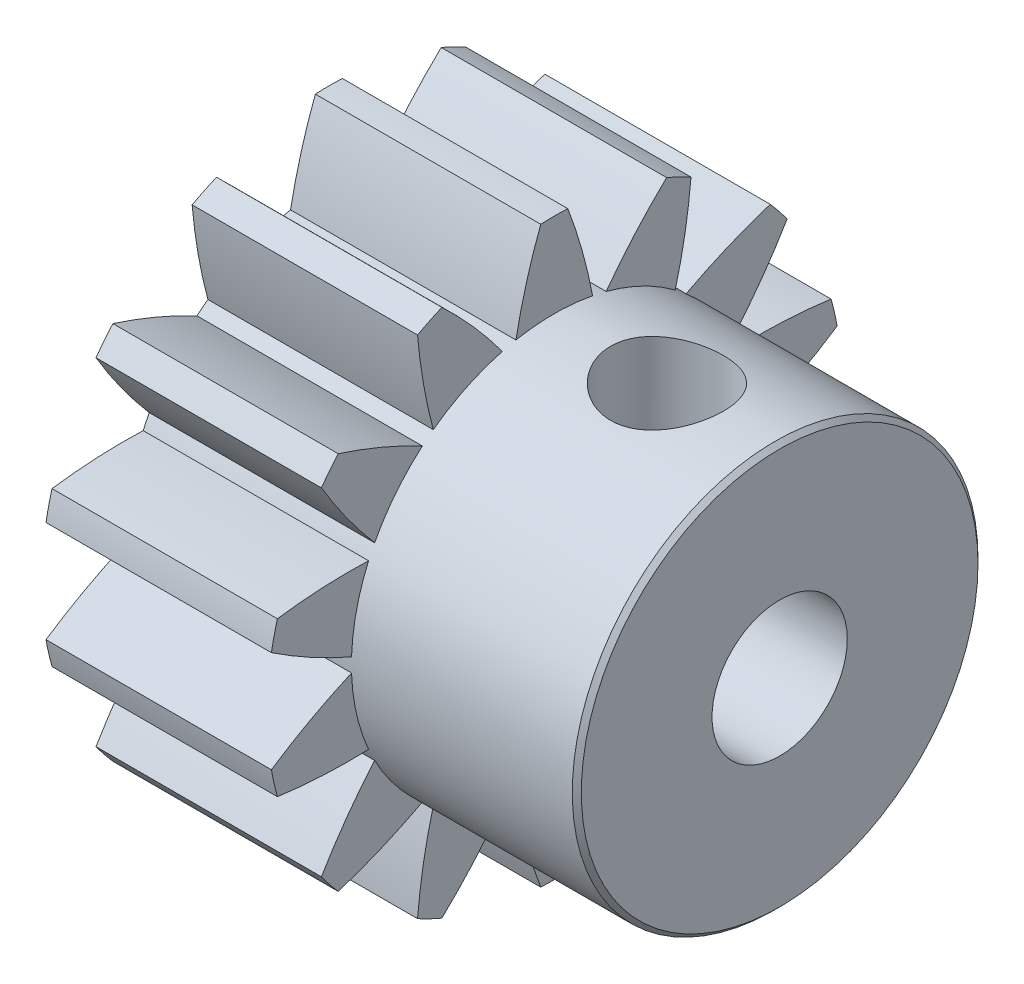
SolidWorks part; units mm, degrees
material "Plain Carbon Steel"
ref_plane "Front Plane" through (0, 0, 0) normal (0, 0, 1) x (1, 0, 0)
ref_plane "Top Plane" through (0, 0, 0) normal (0, 1, 0) x (1, 0, 0)
ref_plane "Right Plane" through (0, 0, 0) normal (1, 0, 0) x (0, 0, -1)
sketch "Sketch1" plane through (0, 0, 0) normal (1, 0, 0) x (0, 0, -1)
  line L0 (0, 0) -> (0, 6.375) construction
  line L1 (0, 0) -> (-0.85, 4.419) construction
  line L2 (0, 0) -> (0.85, 4.419) construction
  circle A0 centre (0, 0) radius 6.375 construction
  circle A1 centre (0, 0) radius 4.5
  arc A2 (-0.3, 6.3679) -> (-0.85, 4.419) centre (10.4497, 2.2822) ccw
  arc A3 (0.3, 6.3679) -> (0.85, 4.419) centre (-10.4497, 2.2822) cw
  arc A4 (-0.85, 4.419) -> (0.85, 4.419) centre (0, 4.2583) ccw
  arc A5 (-0.3, 6.3679) -> (0.3, 6.3679) centre (0, 0) cw
  circle A6 centre (0, 0) radius 1.5
  dimension "D1" = 9
  dimension "D2" = 12.75
  dimension "D4" = 23
  dimension "D6" = 3
  dimension "D3" = 0.85
  dimension "D5" = 0.3
extrude "Boss-Extrude1" add sketch "Sketch1" along normal blind 10 contours A4 A1 A6 | A1 A4 region at (0, -3.3718, 2.7851) region at (0, 4.0046, 0)
extrude "Boss-Extrude2" add sketch "Sketch1<3>" along normal blind 5 contours A5 A2 A1 A3 | A1 A4 region at (0, 4.0046, 0) region at (0, 5.2799, 0)
sketch "Sketch1<3>" plane through (0, 0, 0) normal (1, 0, 0) x (0, 0, -1) same geometry as "Sketch1"
pattern_circular "CirPattern1" count 14 over 360 about axis through (10, 0, 0) along (-1, 0, 0) of "Boss-Extrude2"
sketch "Sketch2" plane through (0, 0, 0) normal (0, 1, 0) x (1, 0, 0)
  line L0 (10, -4.5) -> (10, 4.5) construction
  circle A0 centre (7.5, 0) radius 1.25
  dimension "D1" = 2.5
  dimension "D2" = 2.5
chamfer "Chamfer1" distance 0.1 angle 45 1 edges at (10, 0, -4.5)
extrude "Cut-Extrude1" cut sketch "Sketch2" along normal through all
sketch "Sketch3" plane through (0, 0, 0) normal (-1, 0, 0) x (0, 0, 1)
  circle A0 centre (0, 0) radius 2.5 construction
  text T0 "14T 32P" font "Century Gothic" height 1.5
  dimension "D1" = 5
extrude "Cut-Extrude2" cut sketch "Sketch3" against normal blind 0.01
equation "\"D2@Sketch1\" = \"D1@Sketch1\" / 2.5"
